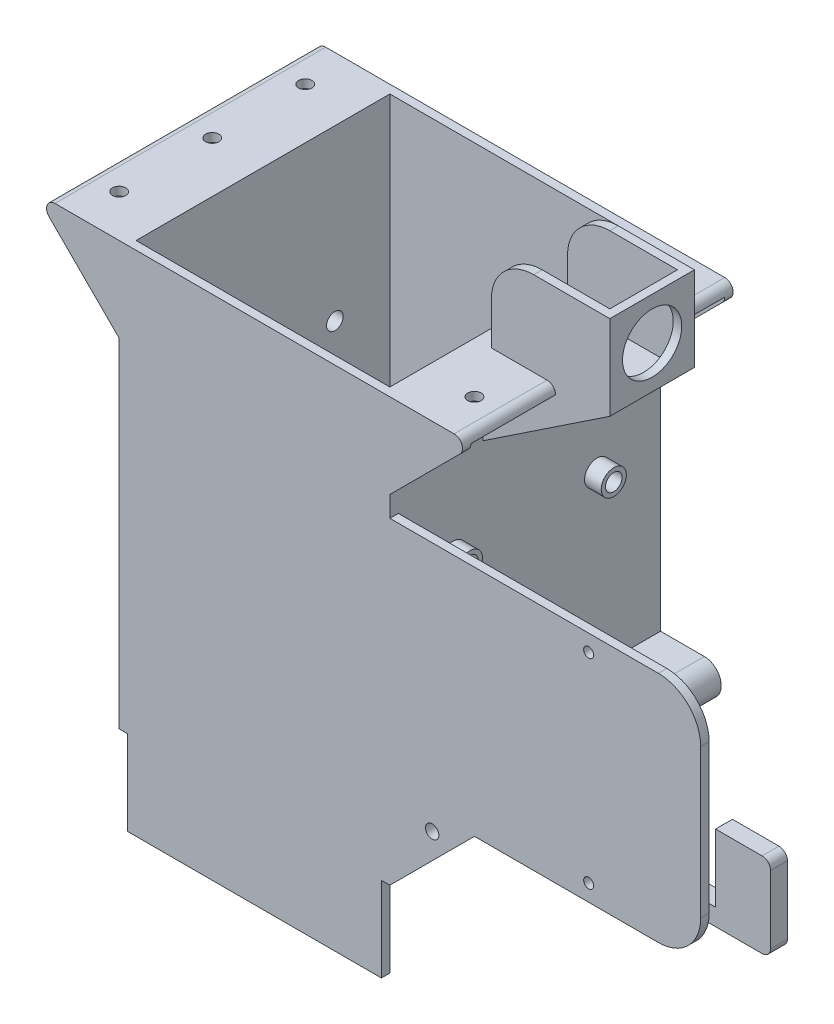
SolidWorks part; units mm, degrees
ref_plane "Front Plane" through (0, 0, 0) normal (0, 0, 1) x (1, 0, 0)
ref_plane "Top Plane" through (0, 0, 0) normal (0, 1, 0) x (1, 0, 0)
ref_plane "Right Plane" through (0, 0, 0) normal (1, 0, 0) x (0, 0, -1)
sketch "Sketch1" plane through (0, 0, 0) normal (0, 1, 0) x (1, 0, 0)
  line L1 (0, 0) -> (81.28, 0)
  line L2 (0, 0) -> (0, 81.28)
  line L3 (0, 81.28) -> (81.28, 81.28)
  line L4 (81.28, 0) -> (81.28, 81.28)
  line L5 (2.54, 2.54) -> (78.74, 2.54)
  line L6 (2.54, 2.54) -> (2.54, 78.74)
  line L7 (2.54, 78.74) -> (78.74, 78.74)
  line L8 (78.74, 2.54) -> (78.74, 78.74)
  dimension "D1" = 2.54
  dimension "D2" = 2.54
  dimension "D3" = 2.54
  dimension "D4" = 2.54
  dimension "D5" = 76.2
  dimension "D6" = 76.2
extrude "Boss-Extrude1" add sketch "Sketch1" along normal blind 177.8
sketch "Sketch2" plane through (0, 0, 0) normal (1, 0, 0) x (0, 0, -1)
  line L0 (109.0297, 38.1) -> (-23.7268, 38.1) construction
  line L1 (81.28, 0) -> (0, 0) construction
  line L2 (40.64, -8.2418) -> (40.64, 63.9342) construction
  line L3 (81.28, 177.8) -> (81.28, 0) construction
  line L5 (66.04, 0) -> (63.5, 0)
  line L6 (66.04, 0) -> (66.04, 38.1)
  line L7 (66.04, 38.1) -> (63.5, 38.1)
  line L8 (63.5, 0) -> (63.5, 38.1)
  dimension "D1" = 38.1
  dimension "D2" = 40.64
  dimension "D3" = 2.54
  dimension "D4" = 15.24
extrude "Boss-Extrude2" add sketch "Sketch2" against normal blind 25.4
sketch "Sketch3" plane through (0, 0, 0) normal (0, 0, 1) x (1, 0, 0)
  line L1 (81.28, 0) -> (78.74, 0)
  line L2 (81.28, 0) -> (81.28, 25.4)
  line L3 (81.28, 25.4) -> (78.74, 25.4)
  line L4 (78.74, 0) -> (78.74, 25.4)
  dimension "D1" = 2.54
  dimension "D2" = 25.4
extrude "Cut-Extrude1" cut sketch "Sketch3" against normal through all
sketch "Sketch7" plane through (0, 0, 0) normal (0, 0, 1) x (1, 0, 0)
  line L0 (81.28, 25.4) -> (106.68, 50.8)
  line L1 (106.68, 50.8) -> (81.28, 50.8)
  line L2 (81.28, 177.8) -> (81.28, 25.4) construction
  line L3 (81.28, 50.8) -> (81.28, 25.4)
  dimension "D1" = 45
  dimension "D2" = 25.4
extrude "Boss-Extrude3" add sketch "Sketch7" against normal blind 12.7
sketch "Sketch10" plane through (0, 0, -81.28) normal (0, 0, -1) x (-1, 0, 0)
  line L0 (-81.28, 25.4) -> (-81.28, 50.8)
  line L1 (-81.28, 177.8) -> (-81.28, 25.4) construction
  line L2 (-81.28, 50.8) -> (-106.68, 50.8)
  line L3 (-106.68, 50.8) -> (-81.28, 25.4)
  dimension "D1" = 45
  dimension "D2" = 25.4
extrude "Boss-Extrude4" add sketch "Sketch10" against normal blind 12.7
sketch "Sketch14" plane through (81.28, 0, 0) normal (1, 0, 0) x (0, 0, -1)
  line L0 (38.1, 50.8) -> (38.1, 25.4)
  line L1 (68.58, 25.4) -> (12.7, 25.4) construction
  line L2 (38.1, 25.4) -> (43.18, 25.4)
  line L3 (43.18, 25.4) -> (43.18, 50.8)
  line L4 (43.18, 50.8) -> (38.1, 50.8)
  line L5 (68.58, 50.8) -> (68.58, 25.4) construction
  dimension "D1" = 5.08
  dimension "D2" = 25.4
  dimension "D3" = 25.4
extrude "Boss-Extrude6" add sketch "Sketch14" along normal blind 76.2
sketch "Sketch16" plane through (0, 0, -38.1) normal (0, 0, 1) x (1, 0, 0)
  line L0 (157.48, 50.8) -> (81.28, 50.8) construction
  line L1 (140.97, 50.8) -> (116.84, 50.8)
  line L2 (140.97, 50.8) -> (140.97, 30.48)
  line L3 (140.97, 30.48) -> (116.84, 30.48)
  line L4 (116.84, 50.8) -> (116.84, 30.48)
  line L5 (157.48, 50.8) -> (157.48, 25.4) construction
  line L6 (157.48, 25.4) -> (81.28, 25.4) construction
  dimension "D1" = 16.51
  dimension "D2" = 24.13
  dimension "D3" = 5.08
extrude "Cut-Extrude2" cut sketch "Sketch16" against normal up to next
sketch "Sketch17" plane through (0, 0, -38.1) normal (0, 0, 1) x (1, 0, 0)
  line L0 (113.03, 59.2483) -> (113.03, 15.3249) construction
  line L1 (116.84, 50.8) -> (116.84, 30.48) construction
  line L2 (116.84, 50.8) -> (81.28, 50.8) construction
  line L3 (113.792, 48.26) -> (115.824, 48.26)
  line L4 (113.792, 48.26) -> (113.792, 33.02)
  line L5 (113.792, 33.02) -> (115.824, 33.02)
  line L6 (115.824, 48.26) -> (115.824, 33.02)
  line L7 (141.732, 48.26) -> (143.764, 48.26)
  line L8 (141.732, 48.26) -> (141.732, 33.02)
  line L9 (141.732, 33.02) -> (143.764, 33.02)
  line L10 (143.764, 48.26) -> (143.764, 33.02)
  line L11 (116.84, 30.48) -> (116.84, 62.58) construction
  line L12 (116.84, 30.48) -> (140.97, 30.48) construction
  line L14 (140.97, 30.48) -> (140.97, 50.8) construction
  dimension "D1" = 3.81
  dimension "D2" = 2.54
  dimension "D3" = 2.54
  dimension "D4" = 0.762
  dimension "D5" = 2.032
  dimension "D6" = 2.032
  dimension "D7" = 0.762
extrude "Cut-Extrude3" [suppressed] cut sketch "Sketch17" against normal up to next
sketch "Sketch22" plane through (0, 0, 0) normal (0, 0, 1) x (1, 0, 0)
  line L0 (93.98, 45.72) -> (101.6, 45.72) construction
  line L1 (106.68, 50.8) -> (81.28, 50.8) construction
  line L2 (93.98, 50.8) -> (93.98, 45.72) construction
  line L4 (81.28, 25.4) -> (106.68, 50.8) construction
  circle A0 centre (93.98, 45.72) radius 2
  point P0 (93.98, 50.8)
  point P10 (93.98, 38.1)
  point P11 (93.2178, 45.72)
  dimension "D3" = 4
  dimension "D1" = 5.08
  dimension "D2" = 12.7
extrude "Cut-Extrude6" cut sketch "Sketch22" against normal through all
sketch "Sketch28" plane through (81.28, 0, 0) normal (1, 0, 0) x (0, 0, -1)
  line L0 (40.64, 175.678) -> (40.64, 120.0937) construction
  line L1 (40.64, 184.0271) -> (40.64, -14.0592) construction
  line L2 (0, 177.8) -> (81.28, 177.8) construction
  line L3 (0, 177.8) -> (0, 50.8) construction
  line L5 (53.34, 177.8) -> (27.94, 177.8)
  line L6 (53.34, 177.8) -> (53.34, 127)
  line L7 (53.34, 127) -> (27.94, 127)
  line L8 (27.94, 177.8) -> (27.94, 127)
  line L9 (53.34, 177.8) -> (27.94, 127) construction
  line L10 (53.34, 127) -> (27.94, 177.8) construction
  point P8 (40.64, 109.22)
  dimension "D2" = 40.64
  dimension "D3" = 50.8
  dimension "D4" = 25.4
extrude "Boss-Extrude7" add sketch "Sketch28" along normal blind 38.1
sketch "Sketch30" plane through (0, 0, -27.94) normal (0, 0, 1) x (1, 0, 0)
  line L0 (81.28, 127) -> (119.38, 127)
  line L1 (119.38, 127) -> (119.38, 152.4)
  line L3 (119.38, 152.4) -> (81.28, 127)
  dimension "D1" = 25.4
  dimension "D2" = 33.69
extrude "Cut-Extrude8" cut sketch "Sketch30" against normal up to next
sketch "Sketch32" plane through (0, 177.8, 0) normal (0, 1, 0) x (1, 0, 0)
  line L0 (119.38, 53.34) -> (81.28, 53.34) construction
  line L1 (83.82, 50.8) -> (116.84, 50.8)
  line L2 (83.82, 50.8) -> (83.82, 30.48)
  line L3 (83.82, 30.48) -> (116.84, 30.48)
  line L4 (116.84, 50.8) -> (116.84, 30.48)
  line L5 (83.82, 50.8) -> (116.84, 30.48) construction
  line L6 (83.82, 30.48) -> (116.84, 50.8) construction
  line L7 (119.38, 53.34) -> (119.38, 27.94) construction
  line L8 (119.38, 27.94) -> (81.28, 27.94) construction
  line L9 (81.28, 53.34) -> (81.28, 81.28) construction
  point P0 (100.33, 40.64)
  dimension "D1" = 2.54
  dimension "D2" = 2.54
  dimension "D3" = 2.54
  dimension "D4" = 2.54
extrude "Cut-Extrude9" cut sketch "Sketch32" against normal blind 25.4
sketch "Sketch34" plane through (119.38, 0, 0) normal (1, 0, 0) x (0, 0, -1)
  line L0 (40.64, 147.7754) -> (40.64, 78.4323) construction
  line L1 (11.6001, 165.1) -> (93.4551, 165.1) construction
  line L2 (27.94, 177.8) -> (27.94, 152.4) construction
  line L3 (53.34, 177.8) -> (27.94, 177.8) construction
  circle A0 centre (40.64, 165.1) radius 8.89
  dimension "D3" = 17.78
  dimension "D1" = 12.7
  dimension "D2" = 12.7
extrude "Cut-Extrude13" cut sketch "Sketch34" against normal up to surface (40.64 mm away) up to face at (78.74, 101.6, -40.64)
sketch "Sketch37" plane through (0, 0, -63.5) normal (0, 0, 1) x (1, 0, 0)
  line L0 (-25.4, 38.1) -> (0, 38.1)
  line L1 (0, 38.1) -> (0, 52.7647)
  line L2 (0, 52.7647) -> (-25.4, 38.1)
  dimension "D1" = 30
extrude "Boss-Extrude9" add sketch "Sketch37" against normal up to surface (2.54 mm away) up to face at (-12.7, 19.05, -66.04)
sketch "Sketch38" plane through (0, 0, 0) normal (0, 0, 1) x (1, 0, 0)
  line L1 (0, 0) -> (2.54, 0)
  line L2 (0, 0) -> (0, 25.4)
  line L3 (0, 25.4) -> (2.54, 25.4)
  line L4 (2.54, 0) -> (2.54, 25.4)
  point P5 (0, 0)
  dimension "D1" = 25.4
  dimension "D2" = 2.54
extrude "Cut-Extrude15" cut sketch "Sketch38" against normal up to surface (63.5 mm away) up to face at (-12.7, 22.7162, -63.5)
sketch "Sketch40" plane through (81.28, 0, 0) normal (1, 0, 0) x (0, 0, -1)
  line L0 (-23.3344, 101.6) -> (103.8421, 101.6) construction
  line L1 (38.1, 25.4) -> (12.7, 25.4) construction
  line L2 (19.05, 177.8) -> (19.05, 25.4) construction
  line L3 (62.23, 177.8) -> (62.23, 25.4) construction
  line L6 (0, 177.8) -> (0, 50.8) construction
  line L7 (81.28, 177.8) -> (81.28, 50.8) construction
  line L8 (0, 177.8) -> (27.94, 177.8) construction
  line L9 (53.34, 177.8) -> (81.28, 177.8) construction
  line L10 (68.58, 25.4) -> (43.18, 25.4) construction
  circle A0 centre (19.05, 101.6) radius 2.5
  circle A1 centre (62.23, 101.6) radius 2.5
  point P16 (19.05, 177.8)
  point P19 (62.23, 177.8)
  point P22 (19.05, 25.4)
  point P23 (62.23, 25.4)
  dimension "D4" = 5
  dimension "D5" = 5
  dimension "D1" = 76.2
  dimension "D2" = 19.05
  dimension "D3" = 19.05
extrude "Cut-Extrude17" cut sketch "Sketch40" against normal up to surface (81.28 mm away) up to face at (0, 63.9912, -52.705)
sketch "Sketch41" plane through (81.28, 0, 0) normal (1, 0, 0) x (0, 0, -1)
  circle A0 centre (19.05, 101.6) radius 3.77
  circle A1 centre (19.05, 101.6) radius 2.5
  circle A2 centre (62.23, 101.6) radius 3.77
  circle A4 centre (62.23, 101.6) radius 2.5
  dimension "D1" = 1.27
  dimension "D2" = 1.27
extrude "Boss-Extrude10" add sketch "Sketch41" along normal blind 5
sketch "Sketch42" plane through (0, 0, 0) normal (-1, 0, 0) x (0, 0, 1)
  circle A0 centre (-62.23, 101.6) radius 2.5
  circle A1 centre (-62.23, 101.6) radius 3.77
  circle A2 centre (-19.05, 101.6) radius 2.5
  circle A3 centre (-19.05, 101.6) radius 3.77
  dimension "D1" = 1.27
  dimension "D2" = 1.27
extrude "Boss-Extrude11" add sketch "Sketch42" along normal blind 5
sketch "Sketch43" plane through (0, 177.8, 0) normal (0, 1, 0) x (1, 0, 0)
  line L1 (83.82, 53.34) -> (83.82, 27.94)
  line L3 (78.74, 2.54) -> (2.54, 2.54)
  line L4 (2.54, 2.54) -> (78.74, 2.54) construction
  line L5 (2.54, 2.54) -> (2.54, 78.74)
  line L6 (2.54, 78.74) -> (78.74, 78.74)
  line L11 (81.28, 81.28) -> (0, 81.28)
  line L12 (0, 81.28) -> (0, 0)
  line L13 (0, 0) -> (81.28, 0)
  line L19 (81.28, 81.28) -> (81.28, 53.34)
  line L21 (81.28, 53.34) -> (83.82, 53.34)
  line L22 (81.28, 0) -> (81.28, 27.94)
  line L23 (81.28, 27.94) -> (83.82, 27.94)
  line L24 (78.74, 78.74) -> (78.74, 2.54)
  line L25 (83.82, 50.8) -> (83.82, 30.48) construction
  line L26 (119.38, 27.94) -> (81.28, 27.94) construction
  line L27 (81.28, 81.28) -> (0, 81.28) construction
  point P3 (81.28, 53.34)
  point P4 (83.82, 53.34)
  point P15 (83.82, 27.94)
  point P19 (81.28, 81.28)
  point P25 (81.28, 0)
extrude "Cut-Extrude20" cut sketch "Sketch43" against normal blind 25.4
sketch "Sketch44" plane through (0, 0, 0) normal (0, 0, 1) x (1, 0, 0)
  line L0 (0, 152.4) -> (0, 25.4) construction
  line L1 (0, 50.8) -> (174.6, 50.8)
  line L2 (0, 50.8) -> (0, 120.8)
  line L3 (0, 120.8) -> (174.6, 120.8)
  line L4 (174.6, 50.8) -> (174.6, 120.8)
  line L5 (106.68, 50.8) -> (81.28, 50.8) construction
  line L6 (-25.4, 38.1) -> (-25.4, 0) construction
  line L7 (140.97, 50.8) -> (140.97, 120.8) construction
  line L8 (140.97, 30.48) -> (140.97, 50.8) construction
  circle A0 centre (140.97, 115.8) radius 1.5
  circle A1 centre (140.97, 55.8) radius 1.5
  dimension "D3" = 3
  dimension "D1" = 200
  dimension "D2" = 70
  dimension "D4" = 60
  dimension "D5" = 5
extrude "Boss-Extrude12" add sketch "Sketch44" against normal blind 2.54
sketch "Sketch45" plane through (0, 0, 0) normal (0, 0, 1) x (1, 0, 0)
  line L0 (0, 152.4) -> (-25.4, 152.4)
  line L1 (-25.4, 152.4) -> (0, 127)
  line L2 (0, 152.4) -> (0, 25.4) construction
  line L3 (0, 127) -> (0, 152.4)
  point P6 (-20.8806, 152.4)
  point P7 (-38.2091, 152.4)
  dimension "D1" = 25.4
  dimension "D2" = 45
extrude "Boss-Extrude13" add sketch "Sketch45" against normal blind 2.54
sketch "Sketch46" plane through (0, 0, -81.28) normal (0, 0, -1) x (-1, 0, 0)
  line L0 (0, 152.4) -> (0, 127)
  line L1 (0, 127) -> (25.4, 152.4)
  line L2 (25.4, 152.4) -> (0, 152.4)
extrude "Boss-Extrude14" add sketch "Sketch46" against normal blind 2.54
sketch "Sketch47" plane through (0, 0, 0) normal (0, 0, 1) x (1, 0, 0)
  line L0 (0, 152.4) -> (-25.4, 152.4)
  line L1 (-25.4, 152.4) -> (81.28, 152.4) construction
  line L2 (-25.4, 152.4) -> (-22.86, 149.86)
  line L3 (-25.4, 152.4) -> (0, 127) construction
  line L4 (-22.86, 149.86) -> (0, 149.86)
  line L5 (0, 149.86) -> (0, 152.4)
  line L6 (0, 127) -> (0, 25.4) construction
  dimension "D1" = 2.54
extrude "Boss-Extrude15" add sketch "Sketch47" against normal through all
sketch "Sketch48" plane through (0, 0, 0) normal (0, 0, 1) x (1, 0, 0)
  line L0 (81.28, 152.4) -> (106.68, 152.4)
  line L1 (106.68, 152.4) -> (81.28, 127)
  line L2 (81.28, 152.4) -> (81.28, 127) construction
  line L3 (81.28, 127) -> (81.28, 152.4)
  dimension "D1" = 25.4
  dimension "D2" = 45
extrude "Boss-Extrude16" add sketch "Sketch48" against normal blind 2.54
sketch "Sketch49" plane through (0, 0, -81.28) normal (0, 0, -1) x (-1, 0, 0)
  line L0 (-81.28, 152.4) -> (-106.68, 152.4)
  line L1 (-106.68, 152.4) -> (-81.28, 127)
  line L2 (-81.28, 127) -> (-81.28, 152.4) construction
  line L3 (-81.28, 127) -> (-81.28, 152.4)
  dimension "D1" = 25.4
  dimension "D2" = 45
extrude "Boss-Extrude17" add sketch "Sketch49" against normal blind 2.54
sketch "Sketch50" plane through (0, 0, -81.28) normal (0, 0, -1) x (-1, 0, 0)
  line L0 (-81.28, 152.4) -> (-106.68, 152.4)
  line L1 (-106.68, 152.4) -> (25.4, 152.4) construction
  line L2 (-106.68, 152.4) -> (-81.28, 127) construction
  line L3 (-106.68, 152.4) -> (-104.14, 149.86)
  line L4 (-104.14, 149.86) -> (-81.28, 149.86)
  line L5 (-81.28, 149.86) -> (-81.28, 152.4)
  line L6 (-81.28, 127) -> (-81.28, 50.8) construction
  dimension "D1" = 2.54
extrude "Boss-Extrude18" add sketch "Sketch50" against normal through all
sketch "Sketch51" plane through (0, 152.4, 0) normal (0, 1, 0) x (1, 0, 0)
  line L0 (-12.7, 81.28) -> (-12.7, 0) construction
  line L1 (-25.4, 0) -> (106.68, 0) construction
  line L2 (106.68, 81.28) -> (-25.4, 81.28) construction
  line L3 (93.98, 0) -> (93.98, 81.28) construction
  line L4 (-25.4, 81.28) -> (-25.4, 0) construction
  line L5 (106.68, 53.34) -> (106.68, 81.28) construction
  line L6 (-25.4003, 68.58) -> (106.68, 68.58) construction
  line L7 (-25.4, 40.64) -> (116.84, 40.64) construction
  line L8 (116.84, 30.48) -> (116.84, 50.8) construction
  line L9 (-25.4, 12.7) -> (106.68, 12.7) construction
  line L10 (106.68, 27.94) -> (106.68, 0) construction
  circle A0 centre (-12.7, 68.58) radius 2
  circle A1 centre (-12.7, 40.64) radius 2
  circle A2 centre (-12.7, 12.7) radius 2
  circle A3 centre (93.98, 68.58) radius 2
  circle A4 centre (93.98, 12.7) radius 2
  point P33 (-12.7, 12.7)
  point P34 (-12.7, 12.7)
  point P35 (106.68, 67.31)
  dimension "D5" = 4
  dimension "D1" = 12.7
  dimension "D2" = 12.7
  dimension "D3" = 12.7
  dimension "D4" = 12.7
extrude "Cut-Extrude21" cut sketch "Sketch51" against normal blind 2.54
fillet "Fillet1" radius 5.08 2 edges at (106.68, 50.8, -7.62) (106.68, 50.8, -74.93)
fillet "Fillet2" radius 12.7 2 edges at (174.6, 120.8, -1.27) (174.6, 50.8, -1.27)
fillet "Fillet3" radius 2.54 2 edges at (157.48, 50.8, -40.64) (157.48, 25.4, -40.64)
fillet "Fillet4" radius 2.54 1 edges at (-25.4, 152.4, -40.64)
fillet "Fillet5" radius 2.54 2 edges at (106.68, 152.4, -67.31) (106.68, 152.4, -13.97)
fillet "Fillet7" radius 12.7 1 edges at (-25.4, 38.1, -64.77)
fillet "Fillet9" radius 12.7 2 edges at (83.82, 177.8, -29.21) (83.82, 177.8, -52.07)
